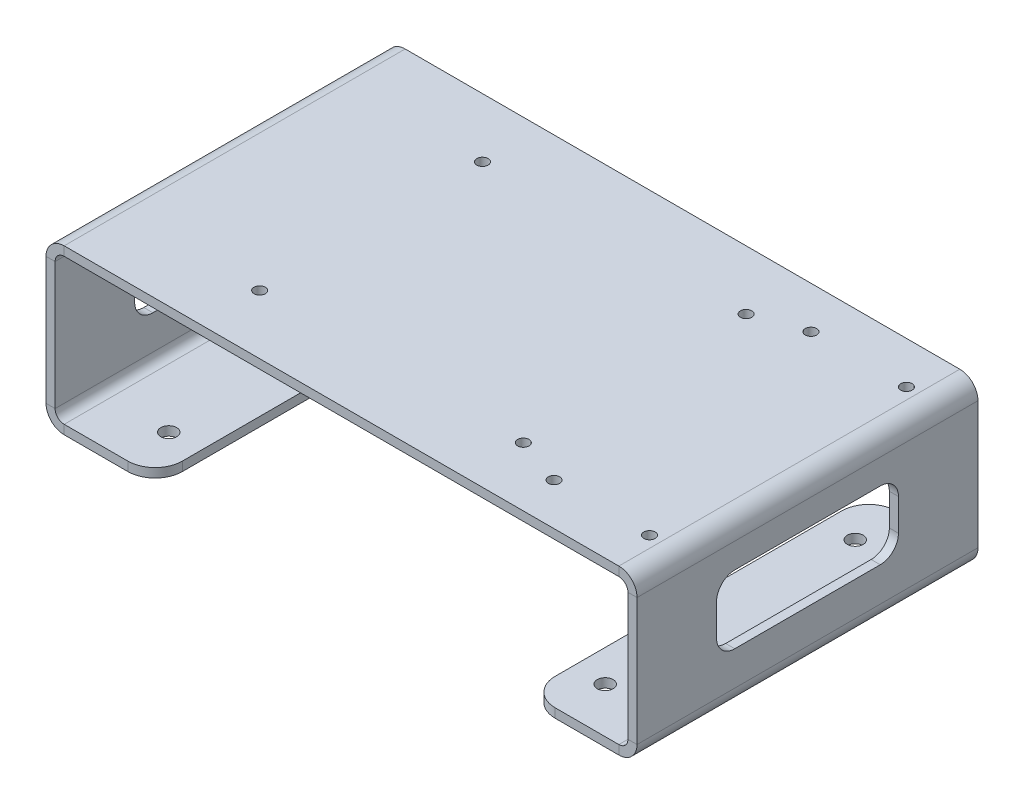
SolidWorks part; units mm, degrees
note: The reader was unsure of these and kept them because the rebuilt part matched: flange length of "Edge-Flange1", "Edge-Flange2", "Edge-Flange3", "Edge-Flange4".
material "1060 Alloy"
ref_plane "Front" through (0, 0, 0) normal (0, 0, 1) x (1, 0, 0)
ref_plane "Top" through (0, 0, 0) normal (0, 1, 0) x (1, 0, 0)
ref_plane "Right" through (0, 0, 0) normal (1, 0, 0) x (0, 0, -1)
sketch "Sketch1" plane through (0, 0, 0) normal (0, 1, 0) x (1, 0, 0)
  line L1 (-65, 37.5) -> (65, 37.5)
  line L2 (-65, 37.5) -> (-65, -37.5)
  line L3 (-65, -37.5) -> (65, -37.5)
  line L4 (65, 37.5) -> (65, -37.5)
  line L5 (-65, 37.5) -> (65, -37.5) construction
  line L6 (-65, -37.5) -> (65, 37.5) construction
  point P0 (0, 0)
  dimension "D1" = 75
  dimension "D2" = 130
base flange "Base-Flange1" sketch "Sketch1" thickness 2 reverse thickness direction no parameters "D1"=2
edge flange "Edge-Flange1" sketch "Sketch10" flange angle 90 flange length 34 flange position material inside bend radius 2 thickness 2 relief rectangular parameters "D6"=10
sketch "Sketch10" plane through (-65, -2, 0) normal (1, 0, 0) x (0, 0, 1)
  line L2 (-37.5, 0) -> (-37.5, 32)
  line L3 (-37.5, 32) -> (37.5, 32)
  line L4 (37.5, 32) -> (37.5, 0)
  line L5 (37.5, 0) -> (-37.5, 0) construction
  line L6 (37.5, 0) -> (-37.5, 0)
bend "EdgeBend1" bend radius 2 bend angle 90 parameters "D5"=1
edge flange "Edge-Flange2" sketch "Sketch13" flange angle 90 flange length 24 flange position material outside bend radius 2 thickness 2 relief rectangular parameters "D6"=10
sketch "Sketch13" plane through (-63, -34, 0) normal (0, -1, 0) x (0, 0, -1)
  line L2 (-37.5, 0) -> (-37.5, 22)
  line L3 (-37.5, 22) -> (37.5, 22)
  line L4 (37.5, 22) -> (37.5, 0)
  line L7 (-37.5, 0) -> (37.5, 0) construction
  line L8 (-37.5, 0) -> (37.5, 0)
bend "EdgeBend2" bend radius 2 bend angle 90 parameters "D5"=2
edge flange "Edge-Flange3" sketch "Sketch16" flange angle 90 flange length 34 flange position material inside bend radius 2 thickness 2 relief rectangular parameters "D6"=10
sketch "Sketch16" plane through (65, -2, 0) normal (-1, 0, 0) x (0, 0, -1)
  line L2 (-37.5, 0) -> (-37.5, 32)
  line L3 (-37.5, 32) -> (37.5, 32)
  line L4 (37.5, 32) -> (37.5, 0)
  line L5 (37.5, 0) -> (-37.5, 0) construction
  line L6 (37.5, 0) -> (-37.5, 0)
bend "EdgeBend3" bend radius 2 bend angle 90 parameters "D5"=3
edge flange "Edge-Flange4" sketch "Sketch19" flange angle 90 flange length 24 flange position material outside bend radius 2 thickness 2 relief rectangular parameters "D6"=10
sketch "Sketch19" plane through (63, -34, 0) normal (0, -1, 0) x (0, 0, 1)
  line L2 (-37.5, 0) -> (-37.5, 22)
  line L3 (-37.5, 22) -> (37.5, 22)
  line L4 (37.5, 22) -> (37.5, 0)
  line L7 (-37.5, 0) -> (37.5, 0) construction
  line L8 (-37.5, 0) -> (37.5, 0)
bend "EdgeBend4" bend radius 2 bend angle 90 parameters "D5"=4
sketch "Sketch20" plane through (0, -34, 0) normal (0, 1, 0) x (1, 0, 0)
  line L0 (61, 37.5) -> (-61, 37.5) construction
  line L1 (-61, -37.5) -> (61, -37.5) construction
  line L2 (-41, 37.5) -> (-41, -37.5) construction
  circle A0 centre (-48, -27.5) radius 1.75
  circle A1 centre (-48, 27.5) radius 1.75
  dimension "D1" = 3.5
  dimension "D2" = 10
  dimension "D3" = 10
  dimension "D4" = 7
extrude "Cut-Extrude1" cut sketch "Sketch20" against normal up to surface (2 mm away) normal cut yes up to face at (-51, -36, 0)
sketch "Sketch21" plane through (-65, 0, 0) normal (-1, 0, 0) x (0, 0, 1)
  line L1 (-16, -9.5) -> (16, -9.5)
  line L2 (-20, -13.5) -> (-20, -20.5)
  line L3 (-16, -24.5) -> (16, -24.5)
  line L4 (20, -13.5) -> (20, -20.5)
  line L5 (-20, -9.5) -> (20, -24.5) construction
  line L6 (-20, -24.5) -> (20, -9.5) construction
  arc A0 (16, -9.5) -> (20, -13.5) centre (16, -13.5) cw
  arc A1 (16, -24.5) -> (20, -20.5) centre (16, -20.5) ccw
  arc A2 (-20, -20.5) -> (-16, -24.5) centre (-16, -20.5) ccw
  arc A3 (-16, -9.5) -> (-20, -13.5) centre (-16, -13.5) ccw
  point P0 (0, -17)
  dimension "D4" = 4
  dimension "D1" = 40
  dimension "D2" = 15
  dimension "D3" = 17
extrude "Cut-Extrude2" cut sketch "Sketch21" against normal up to surface (128 mm away)
fillet "Fillet1" radius 6 4 edges at (-41, -35, -37.5) (-41, -35, 37.5) (41, -35, -37.5) (41, -35, 37.5)
mirror "Mirror4" about plane through (0, 0, 0) normal (1, 0, 0) of "Cut-Extrude2", "Cut-Extrude1"
sketch "Sketch22" plane through (0, 0, 0) normal (0, 1, 0) x (1, 0, 0)
  line L1 (-31, 24.5) -> (27, 24.5)
  line L2 (-31, 24.5) -> (-31, -24.5)
  line L3 (-31, -24.5) -> (27, -24.5)
  line L4 (27, 24.5) -> (27, -24.5)
  line L5 (-31, 24.5) -> (27, -24.5) construction
  line L6 (-31, -24.5) -> (27, 24.5) construction
  circle A0 centre (-31, 24.5) radius 1.25
  circle A1 centre (-31, -24.5) radius 1.25
  circle A2 centre (27, -24.5) radius 1.25
  circle A3 centre (27, 24.5) radius 1.25
  point P0 (-2, 0)
  dimension "D4" = 2.5
  dimension "D1" = 2
  dimension "D2" = 49
  dimension "D3" = 58
extrude "Cut-Extrude3" cut sketch "Sketch22" against normal up to surface (2 mm away) contours L1 A0 L2 | L2 A0 L1 | A3 | A2 | A1 normal cut yes up to face at (0, -2, 0)
sketch "Sketch23" plane through (0, 0, 0) normal (0, 1, 0) x (1, 0, 0)
  line L1 (37.5, 28.25) -> (58.5, 28.25)
  line L2 (37.5, 28.25) -> (37.5, -28.25)
  line L3 (37.5, -28.25) -> (58.5, -28.25)
  line L4 (58.5, 28.25) -> (58.5, -28.25)
  line L5 (37.5, 28.25) -> (58.5, -28.25) construction
  line L6 (37.5, -28.25) -> (58.5, 28.25) construction
  line L7 (65, 37.5) -> (65, -37.5) construction
  circle A0 centre (37.5, 28.25) radius 1.25
  circle A1 centre (58.5, 28.25) radius 1.25
  circle A2 centre (37.5, -28.25) radius 1.25
  circle A3 centre (58.5, -28.25) radius 1.25
  point P0 (48, 0)
  dimension "D4" = 2.5
  dimension "D1" = 17
  dimension "D2" = 56.5
  dimension "D3" = 21
extrude "Cut-Extrude4" cut sketch "Sketch23" against normal up to surface (2 mm away) contours L2 A2 L3 | L3 A2 L2 | A0 | A1 | A3 normal cut yes up to face at (-31, -2, 25.75)
sketch "Bend-Lines1" [suppressed] plane through (0, 0, 0) normal (0, 1, 0) x (1, 0, 0)
sketch "Bounding-Box1" [suppressed] plane through (0, 0, 0) normal (0, 1, 0) x (1, 0, 0)
sheet metal parameters "Sheet-Metal1" thickness 2 parameters "D1"=2
flat pattern "Flat-Pattern1" [suppressed]
sketch "Bend-Lines2" plane through (0, 0, 0) normal (0, 1, 0) x (1, 0, 0)
sketch3d "Bounding-Box2" [suppressed]
  line L0 (-65, -37.5, 0) -> (65, -37.5, 0) construction
  line L1 (-65, 37.5, 0) -> (65, 37.5, 0) construction
  line L2 (-65, -37.5, 0) -> (-65, 37.5, 0) construction
  line L3 (65, -37.5, 0) -> (65, 37.5, 0) construction
sheet metal parameters "Sheet-Metal2" thickness 2 parameters "D1"=2
flat pattern "Flat-Pattern1"
sketch "Bend-Lines2" plane through (0, 0, 0) normal (0, 1, 0) x (1, 0, 0)
  line L0 (-63.3562, 37.5) -> (-63.3562, -37.5) construction
  line L1 (-63.3562, 37.5) -> (-63.3562, -37.5) construction
sketch3d "Bounding-Box2" [suppressed]
  line L0 (65, -37.5, 0) -> (-93.7124, -37.5, 0) construction
  line L1 (65, 37.5, 0) -> (-93.7124, 37.5, 0) construction
  line L2 (65, -37.5, 0) -> (65, 37.5, 0) construction
  line L3 (-93.7124, -37.5, 0) -> (-93.7124, 37.5, 0) construction
bend of the flat pattern "Flatten-<EdgeBend1>1"
sheet metal parameters "Sheet-Metal3" thickness 2 parameters "D1"=2
flat pattern "Flat-Pattern1"
sketch "Bend-Lines2" plane through (0, 0, 0) normal (0, 1, 0) x (1, 0, 0)
  line L0 (-63.3562, 37.5) -> (-63.3562, -37.5) construction
  line L1 (-63.3562, 37.5) -> (-63.3562, -37.5) construction
  line L2 (-94.0686, 37.5) -> (-94.0686, -37.5) construction
  line L3 (-94.0686, 37.5) -> (-94.0686, -37.5) construction
sketch3d "Bounding-Box2" [suppressed]
  line L0 (65, -37.5, 0) -> (-116.4248, -37.5, 0) construction
  line L1 (65, 37.5, 0) -> (-116.4248, 37.5, 0) construction
  line L2 (65, -37.5, 0) -> (65, 37.5, 0) construction
  line L3 (-116.4248, -37.5, 0) -> (-116.4248, 37.5, 0) construction
bend of the flat pattern "Flatten-<EdgeBend1>1"
bend of the flat pattern "Flatten-<EdgeBend2>1"
sheet metal parameters "Sheet-Metal4" thickness 2 parameters "D1"=2
flat pattern "Flat-Pattern1"
sketch "Bend-Lines2" plane through (0, 0, 0) normal (0, 1, 0) x (1, 0, 0)
  line L0 (-63.3562, 37.5) -> (-63.3562, -37.5) construction
  line L1 (-63.3562, 37.5) -> (-63.3562, -37.5) construction
  line L2 (-94.0686, 37.5) -> (-94.0686, -37.5) construction
  line L3 (-94.0686, 37.5) -> (-94.0686, -37.5) construction
  line L4 (63.3562, -37.5) -> (63.3562, 37.5) construction
  line L5 (63.3562, -37.5) -> (63.3562, 37.5) construction
sketch3d "Bounding-Box2" [suppressed]
  line L0 (93.7124, -37.5, 0) -> (-116.4248, -37.5, 0) construction
  line L1 (93.7124, 37.5, 0) -> (-116.4248, 37.5, 0) construction
  line L2 (93.7124, -37.5, 0) -> (93.7124, 37.5, 0) construction
  line L3 (-116.4248, -37.5, 0) -> (-116.4248, 37.5, 0) construction
bend of the flat pattern "Flatten-<EdgeBend1>1"
bend of the flat pattern "Flatten-<EdgeBend2>1"
bend of the flat pattern "Flatten-<EdgeBend3>1"
sheet metal parameters "Sheet-Metal5" thickness 2 parameters "D1"=2
flat pattern "Flat-Pattern1"
sketch "Bend-Lines2" plane through (0, 0, 0) normal (0, 1, 0) x (1, 0, 0)
  line L0 (-63.3562, 37.5) -> (-63.3562, -37.5) construction
  line L1 (-63.3562, 37.5) -> (-63.3562, -37.5) construction
  line L2 (-96.0686, 37.5) -> (-96.0686, -37.5) construction
  line L3 (-96.0686, 37.5) -> (-96.0686, -37.5) construction
  line L4 (63.3562, -37.5) -> (63.3562, 37.5) construction
  line L5 (63.3562, -37.5) -> (63.3562, 37.5) construction
  line L6 (96.0686, -37.5) -> (96.0686, 37.5) construction
  line L7 (96.0686, -37.5) -> (96.0686, 37.5) construction
sketch3d "Bounding-Box2" [suppressed]
  line L0 (118.4248, -37.5, 0) -> (-118.4248, -37.5, 0) construction
  line L1 (118.4248, 37.5, 0) -> (-118.4248, 37.5, 0) construction
  line L2 (118.4248, -37.5, 0) -> (118.4248, 37.5, 0) construction
  line L3 (-118.4248, -37.5, 0) -> (-118.4248, 37.5, 0) construction
bend of the flat pattern "Flatten-<EdgeBend1>1"
bend of the flat pattern "Flatten-<EdgeBend2>1"
bend of the flat pattern "Flatten-<EdgeBend3>1"
bend of the flat pattern "Flatten-<EdgeBend4>1"
sheet metal parameters "Sheet-Metal6" thickness 2 parameters "D1"=2
flat pattern "Flat-Pattern1"
sketch "Bend-Lines2" plane through (0, 0, 0) normal (0, 1, 0) x (1, 0, 0)
  line L0 (-63.3562, 37.5) -> (-63.3562, -37.5) construction
  line L1 (-63.3562, 37.5) -> (-63.3562, -37.5) construction
  line L2 (-96.0686, 37.5) -> (-96.0686, -37.5) construction
  line L3 (-96.0686, 37.5) -> (-96.0686, -37.5) construction
  line L4 (63.3562, -37.5) -> (63.3562, 37.5) construction
  line L5 (63.3562, -37.5) -> (63.3562, 37.5) construction
  line L6 (96.0686, -37.5) -> (96.0686, 37.5) construction
  line L7 (96.0686, -37.5) -> (96.0686, 37.5) construction
sketch3d "Bounding-Box2" [suppressed]
  line L0 (118.4248, -37.5, 0) -> (-118.4248, -37.5, 0) construction
  line L1 (118.4248, 37.5, 0) -> (-118.4248, 37.5, 0) construction
  line L2 (118.4248, -37.5, 0) -> (118.4248, 37.5, 0) construction
  line L3 (-118.4248, -37.5, 0) -> (-118.4248, 37.5, 0) construction
bend of the flat pattern "Flatten-<EdgeBend1>1"
bend of the flat pattern "Flatten-<EdgeBend2>1"
bend of the flat pattern "Flatten-<EdgeBend3>1"
bend of the flat pattern "Flatten-<EdgeBend4>1"
sheet metal parameters "Sheet-Metal7" thickness 2 parameters "D1"=2
flat pattern "Flat-Pattern1"
sketch "Bend-Lines2" plane through (0, 0, 0) normal (0, 1, 0) x (1, 0, 0)
  line L0 (-63.3562, 37.5) -> (-63.3562, -37.5) construction
  line L1 (-63.3562, 37.5) -> (-63.3562, -37.5) construction
  line L2 (-96.0686, 37.5) -> (-96.0686, -37.5) construction
  line L3 (-96.0686, 37.5) -> (-96.0686, -37.5) construction
  line L4 (63.3562, -37.5) -> (63.3562, 37.5) construction
  line L5 (63.3562, -37.5) -> (63.3562, 37.5) construction
  line L6 (96.0686, -37.5) -> (96.0686, 37.5) construction
  line L7 (96.0686, -37.5) -> (96.0686, 37.5) construction
sketch3d "Bounding-Box2" [suppressed]
  line L0 (-118.4248, -37.5, 0) -> (118.4248, -37.5, 0) construction
  line L1 (-118.4248, 37.5, 0) -> (118.4248, 37.5, 0) construction
  line L2 (-118.4248, -37.5, 0) -> (-118.4248, 37.5, 0) construction
  line L3 (118.4248, -37.5, 0) -> (118.4248, 37.5, 0) construction
bend of the flat pattern "Flatten-<EdgeBend1>1"
bend of the flat pattern "Flatten-<EdgeBend2>1"
bend of the flat pattern "Flatten-<EdgeBend3>1"
bend of the flat pattern "Flatten-<EdgeBend4>1"
sheet metal parameters "Sheet-Metal8" thickness 2 parameters "D1"=2
flat pattern "Flat-Pattern1"
sketch "Bend-Lines2" plane through (0, 0, 0) normal (0, 1, 0) x (1, 0, 0)
  line L0 (-63.3562, 37.5) -> (-63.3562, -37.5) construction
  line L1 (-63.3562, 37.5) -> (-63.3562, -37.5) construction
  line L2 (-96.0686, 37.5) -> (-96.0686, -37.5) construction
  line L3 (-96.0686, 37.5) -> (-96.0686, -37.5) construction
  line L4 (63.3562, -37.5) -> (63.3562, 37.5) construction
  line L5 (63.3562, -37.5) -> (63.3562, 37.5) construction
  line L6 (96.0686, -37.5) -> (96.0686, 37.5) construction
  line L7 (96.0686, -37.5) -> (96.0686, 37.5) construction
sketch3d "Bounding-Box2" [suppressed]
  line L0 (-118.4248, -37.5, 0) -> (118.4248, -37.5, 0) construction
  line L1 (-118.4248, 37.5, 0) -> (118.4248, 37.5, 0) construction
  line L2 (-118.4248, -37.5, 0) -> (-118.4248, 37.5, 0) construction
  line L3 (118.4248, -37.5, 0) -> (118.4248, 37.5, 0) construction
bend of the flat pattern "Flatten-<EdgeBend1>1"
bend of the flat pattern "Flatten-<EdgeBend2>1"
bend of the flat pattern "Flatten-<EdgeBend3>1"
bend of the flat pattern "Flatten-<EdgeBend4>1"
sheet metal parameters "Sheet-Metal9" thickness 2 parameters "D1"=2
flat pattern "Flat-Pattern1"
sketch "Bend-Lines2" plane through (0, 0, 0) normal (0, 1, 0) x (1, 0, 0)
  line L0 (-63.3562, 37.5) -> (-63.3562, -37.5) construction
  line L1 (-63.3562, 37.5) -> (-63.3562, -37.5) construction
  line L2 (-96.0686, 37.5) -> (-96.0686, -37.5) construction
  line L3 (-96.0686, 37.5) -> (-96.0686, -37.5) construction
  line L4 (63.3562, -37.5) -> (63.3562, 37.5) construction
  line L5 (63.3562, -37.5) -> (63.3562, 37.5) construction
  line L6 (96.0686, -37.5) -> (96.0686, 37.5) construction
  line L7 (96.0686, -37.5) -> (96.0686, 37.5) construction
sketch3d "Bounding-Box2" [suppressed]
  line L0 (-118.4248, -37.5, 0) -> (118.4248, -37.5, 0) construction
  line L1 (-118.4248, 37.5, 0) -> (118.4248, 37.5, 0) construction
  line L2 (-118.4248, -37.5, 0) -> (-118.4248, 37.5, 0) construction
  line L3 (118.4248, -37.5, 0) -> (118.4248, 37.5, 0) construction
bend of the flat pattern "Flatten-<EdgeBend1>1"
bend of the flat pattern "Flatten-<EdgeBend2>1"
bend of the flat pattern "Flatten-<EdgeBend3>1"
bend of the flat pattern "Flatten-<EdgeBend4>1"
sheet metal parameters "Sheet-Metal10" thickness 2 parameters "D1"=2
flat pattern "Flat-Pattern1"
sketch "Bend-Lines2" plane through (0, 0, 0) normal (0, 1, 0) x (1, 0, 0)
  line L0 (-63.3562, 37.5) -> (-63.3562, -37.5) construction
  line L1 (-63.3562, 37.5) -> (-63.3562, -37.5) construction
  line L2 (-96.0686, 37.5) -> (-96.0686, -37.5) construction
  line L3 (-96.0686, 37.5) -> (-96.0686, -37.5) construction
  line L4 (63.3562, -37.5) -> (63.3562, 37.5) construction
  line L5 (63.3562, -37.5) -> (63.3562, 37.5) construction
  line L6 (96.0686, -37.5) -> (96.0686, 37.5) construction
  line L7 (96.0686, -37.5) -> (96.0686, 37.5) construction
sketch3d "Bounding-Box2" [suppressed]
  line L0 (-118.4248, -37.5, 0) -> (118.4248, -37.5, 0) construction
  line L1 (-118.4248, 37.5, 0) -> (118.4248, 37.5, 0) construction
  line L2 (-118.4248, -37.5, 0) -> (-118.4248, 37.5, 0) construction
  line L3 (118.4248, -37.5, 0) -> (118.4248, 37.5, 0) construction
bend of the flat pattern "Flatten-<EdgeBend1>1"
bend of the flat pattern "Flatten-<EdgeBend2>1"
bend of the flat pattern "Flatten-<EdgeBend3>1"
bend of the flat pattern "Flatten-<EdgeBend4>1"
